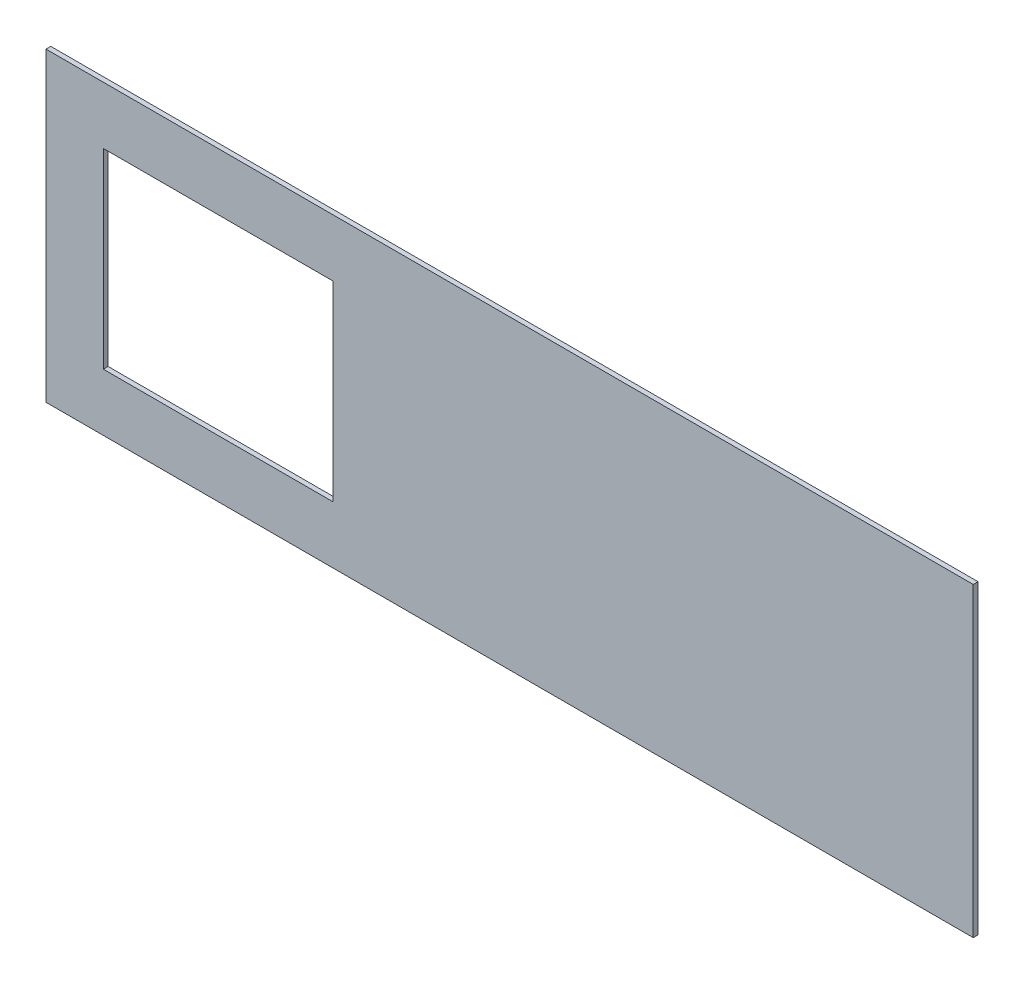
SolidWorks part; units mm, degrees
ref_plane "Front Plane" through (0, 0, 0) normal (0, 0, 1) x (1, 0, 0)
ref_plane "Top Plane" through (0, 0, 0) normal (0, 1, 0) x (1, 0, 0)
ref_plane "Right Plane" through (0, 0, 0) normal (1, 0, 0) x (0, 0, -1)
sketch "Sketch1" plane through (0, 0, 0) normal (0, 0, 1) x (1, 0, 0)
  line L1 (-307.975, -101.6) -> (307.975, -101.6)
  line L2 (-307.975, -101.6) -> (-307.975, 101.6)
  line L3 (-307.975, 101.6) -> (307.975, 101.6)
  line L4 (307.975, -101.6) -> (307.975, 101.6)
  line L5 (-307.975, -101.6) -> (307.975, 101.6) construction
  line L6 (-307.975, 101.6) -> (307.975, -101.6) construction
  point P0 (0, 0)
  dimension "D1" = 203.2
  dimension "D2" = 615.95
extrude "Boss-Extrude1" add sketch "Sketch1" along normal blind 3.175
sketch "Sketch2" plane through (0, 0, 3.175) normal (0, 0, 1) x (1, 0, 0)
  line L0 (307.975, 101.6) -> (-307.975, 101.6) construction
  line L1 (-269.875, -63.5) -> (-117.475, -63.5)
  line L2 (-269.875, -63.5) -> (-269.875, 63.5)
  line L3 (-269.875, 63.5) -> (-117.475, 63.5)
  line L4 (-117.475, -63.5) -> (-117.475, 63.5)
  line L5 (-307.975, 101.6) -> (-307.975, -101.6) construction
  dimension "D1" = 38.1
  dimension "D2" = 38.1
  dimension "D3" = 127
  dimension "D4" = 152.4
extrude "Cut-Extrude1" cut sketch "Sketch2" against normal through all
